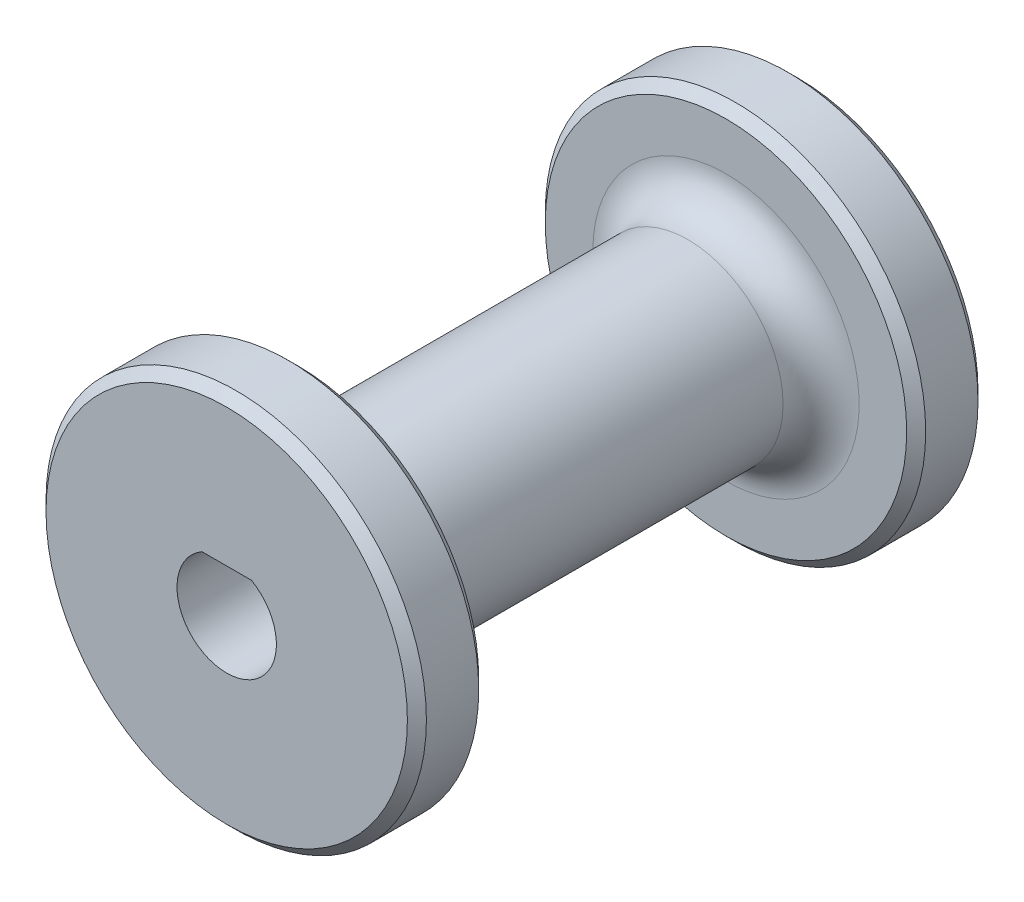
SolidWorks part; units mm, degrees
ref_plane "Front Plane" through (0, 0, 0) normal (0, 0, 1) x (1, 0, 0)
ref_plane "Top Plane" through (0, 0, 0) normal (0, 1, 0) x (1, 0, 0)
ref_plane "Right Plane" through (0, 0, 0) normal (1, 0, 0) x (0, 0, -1)
sketch "Sketch1" plane through (0, 0, 0) normal (0, 0, 1) x (1, 0, 0)
  circle A0 centre (0, 0) radius 3.3175
  circle A1 centre (0, 0) radius 6.35
  dimension "D1" = 6.635
  dimension "D2" = 12.7
extrude "Boss-Extrude1" add sketch "Sketch1" along normal blind 14.2875 and the other way blind 14.2875 contours A1 A0 region at (-6.1704, 0, 0)
sketch "Sketch2" plane through (0, 0, -14.2875) normal (0, 0, -1) x (-1, 0, 0)
  circle A0 centre (0, 0) radius 12.7
  circle A1 centre (0, 0) radius 6.35 construction
  circle A2 centre (0, 0) radius 6.35 construction
  circle A3 centre (0, 0) radius 3.3175 construction
  circle A4 centre (0, 0) radius 3.3175
  circle M3 centre (0, 0) radius 3.3175
  circle M4 centre (0, 0) radius 6.35
  dimension "D1" = 6.35
extrude "Boss-Extrude3" add sketch "Sketch2" along normal blind 4.7625 contours M4 M3 | A0 M4 region at (12.3408, 0, -14.2875) region at (6.1704, 0, -14.2875)
mirror "Mirror1" about plane through (0, 0, 0) normal (0, 0, 1) of "Boss-Extrude3"
sketch "Sketch3" plane through (0, 0, -19.05) normal (0, 0, -1) x (-1, 0, 0)
  circle A0 centre (0, 0) radius 3.3175 construction
  circle A1 centre (0, 0) radius 3.3175
extrude "Boss-Extrude4" add sketch "Sketch3" against normal blind 24.13
fillet "Fillet1" radius 2.54 2 edges at (6.35, 0, 14.2875) (6.35, 0, -14.2875)
chamfer "Chamfer1" distance 0.635 angle 45 4 edges at (-12.7, 0, -19.05) (-12.7, 0, -14.2875) (-12.7, 0, 14.2875) (-12.7, 0, 19.05)
sketch "Sketch4" plane through (0, 0, 19.05) normal (0, 0, 1) x (1, 0, 0)
  line L0 (-1.651, 2.8775) -> (1.651, 2.8775)
  circle A0 centre (0, 0) radius 3.3175 construction
  circle A1 centre (0, 0) radius 3.3175
  circle M3 centre (0, 0) radius 3.3175
  dimension "D1" = 3.302
extrude "Boss-Extrude5" add sketch "Sketch4" against normal up to next contours L0 M3 region at (0, 3.0545, 19.05)
